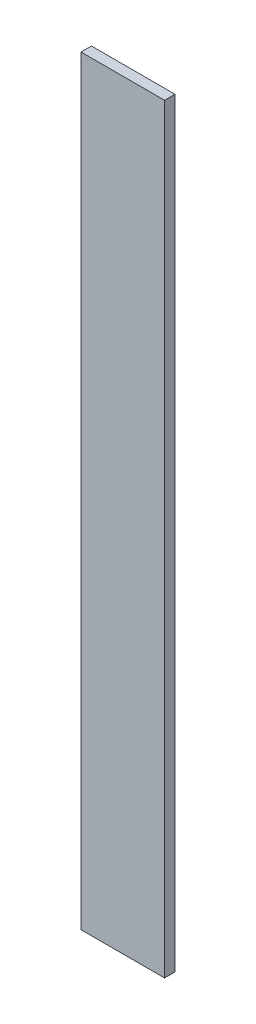
SolidWorks part; units mm, degrees
ref_plane "Front Plane" through (0, 0, 0) normal (0, 0, 1) x (1, 0, 0)
ref_plane "Top Plane" through (0, 0, 0) normal (0, 1, 0) x (1, 0, 0)
ref_plane "Right Plane" through (0, 0, 0) normal (1, 0, 0) x (0, 0, -1)
sketch "Sketch1" plane through (0, 0, 0) normal (0, 1, 0) x (1, 0, 0)
  line L1 (12.7, -1.5875) -> (-12.7, -1.5875)
  line L2 (12.7, -1.5875) -> (12.7, 1.5875)
  line L3 (12.7, 1.5875) -> (-12.7, 1.5875)
  line L4 (-12.7, -1.5875) -> (-12.7, 1.5875)
  line L5 (12.7, -1.5875) -> (-12.7, 1.5875) construction
  line L6 (12.7, 1.5875) -> (-12.7, -1.5875) construction
  point P0 (0, 0)
  dimension "D1" = 12.7
  dimension "D2" = 3.175
extrude "Boss-Extrude1" add sketch "Sketch1" along normal blind 231.14
